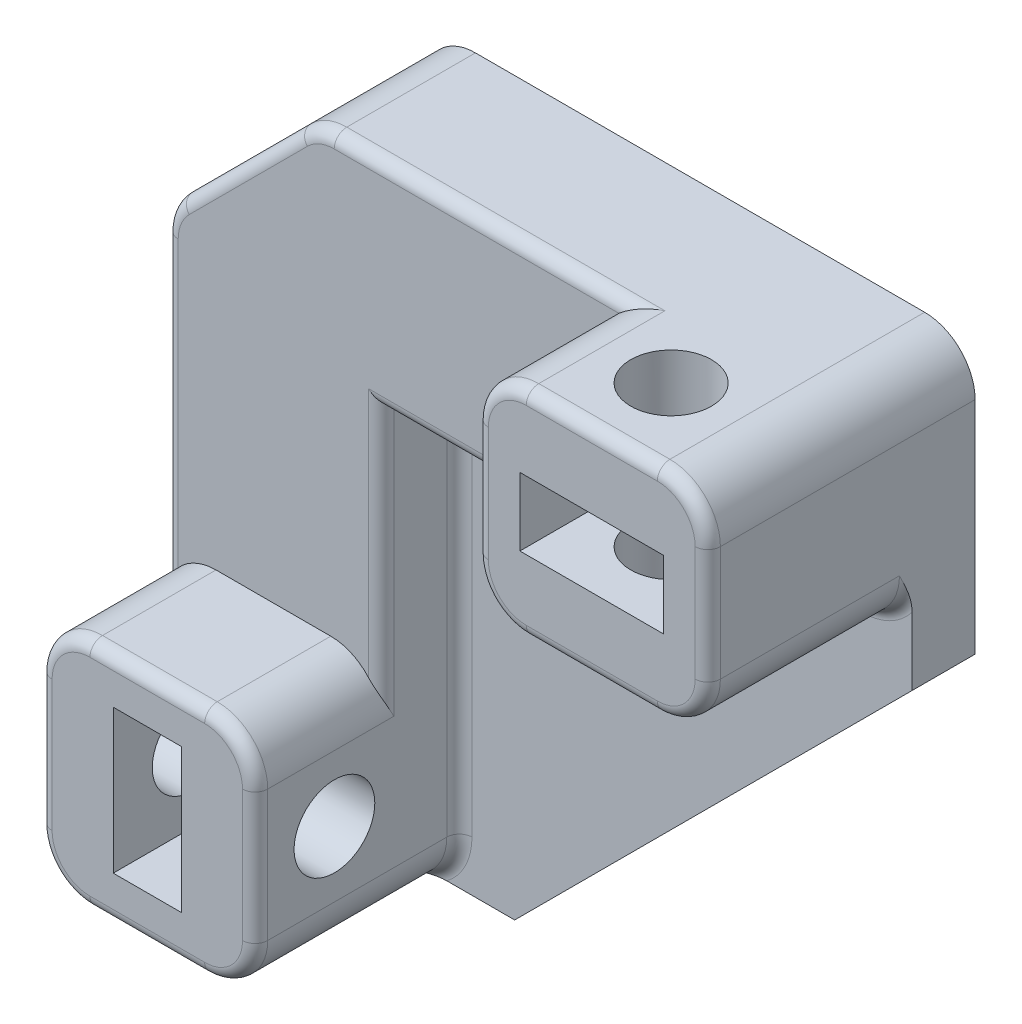
SolidWorks part; units mm, degrees
ref_plane "Plano frontal" through (0, 0, 0) normal (0, 0, 1) x (1, 0, 0)
ref_plane "Plano superior" through (0, 0, 0) normal (0, 1, 0) x (1, 0, 0)
ref_plane "Plano direito" through (0, 0, 0) normal (1, 0, 0) x (0, 0, -1)
sketch "Esboço1" plane through (0, 0, 0) normal (0, 0, 1) x (1, 0, 0)
  line L107 (-13.25, 6.5637) -> (-13.25, -11.25)
  line L117 (-11.25, -13.25) -> (-2.5074, -13.25)
  line L118 (-2.5074, -13.25) -> (13.25, 2.5074)
  line L119 (13.25, 2.5074) -> (13.25, 11.25)
  line L129 (11.25, 13.25) -> (-6.5637, 13.25)
  line L135 (-7.9779, 12.6642) -> (-12.6642, 7.9779)
  circle A0 centre (0, 0) radius 1.7
  arc A1 (13.25, 11.25) -> (11.25, 13.25) centre (11.25, 11.25) ccw
  arc A2 (-6.5637, 13.25) -> (-7.9779, 12.6642) centre (-6.5637, 11.25) ccw
  arc A3 (-12.6642, 7.9779) -> (-13.25, 6.5637) centre (-11.25, 6.5637) ccw
  arc A4 (-13.25, -11.25) -> (-11.25, -13.25) centre (-11.25, -11.25) ccw
  point P23 (-13.25, -13.25)
  dimension "D1" = 3.4
  dimension "D7" = 2
  dimension "D2" = 7.5962
  dimension "D3" = 135
  dimension "D4" = 22.1924
  dimension "D5" = 26.5
  dimension "D6" = 26.5
  dimension "D8" = 10.7426
  dimension "D9" = 13.25
extrude "Ressalto-extrusão1" add sketch "Esboço1" along normal blind 2.5 contours L135 L107 A1 A2 L117 L118 L119 A3 A4 L129 A0 region at (-1.4497, 1.4497, 0)
ref_plane "Plano1" through (0, 0, 2.5) normal (0, 0, -1) x (-1, 0, 0)
sketch "Esboço5" plane through (0, 0, 2.5) normal (0, 0, -1) x (-1, 0, 0)
  line L0 (-11.25, 4.7) -> (4.7, 4.7)
  line L1 (11.25, -13.25) -> (2.5074, -13.25) construction
  line L2 (4.7, 4.7) -> (4.7, -11.25)
  line L3 (-13.25, 2.5074) -> (-13.25, 11.25) construction
  line L4 (-11.25, 13.25) -> (6.5637, 13.25) construction
  line L5 (13.25, 6.5637) -> (13.25, -11.25) construction
  line L6 (7.9779, 12.6642) -> (12.6642, 7.9779) construction
  line L7 (-13.25, 6.7) -> (-13.25, 11.25)
  line L8 (-11.25, 13.25) -> (6.5637, 13.25)
  line L9 (7.9779, 12.6642) -> (12.6642, 7.9779)
  line L10 (13.25, 6.5637) -> (13.25, -11.25)
  line L11 (11.25, -13.25) -> (6.7, -13.25)
  arc A0 (7.9779, 12.6642) -> (6.5637, 13.25) centre (6.5637, 11.25) ccw construction
  arc A1 (11.25, -13.25) -> (13.25, -11.25) centre (11.25, -11.25) ccw
  arc A2 (13.25, 6.5637) -> (12.6642, 7.9779) centre (11.25, 6.5637) ccw
  arc A3 (7.9779, 12.6642) -> (6.5637, 13.25) centre (6.5637, 11.25) ccw
  arc A8 (4.7, -11.25) -> (6.7, -13.25) centre (6.7, -11.25) ccw
  arc A9 (-11.25, 4.7) -> (-13.25, 6.7) centre (-11.25, 6.7) cw
  arc A10 (-11.25, 13.25) -> (-13.25, 11.25) centre (-11.25, 11.25) ccw
  point P19 (4.7, -13.25)
  point P22 (-13.25, 4.7)
  dimension "D3" = 2
  dimension "D1" = 8.55
  dimension "D2" = 8.55
extrude "Ressalto-extrusão3" add sketch "Esboço5" against normal blind 3.1
sketch "Esboço6" plane through (0, 0, 5.6) normal (0, 0, 1) x (1, 0, 0)
  line L0 (-6.7, -4.05) -> (-11.25, -4.05)
  line L1 (-4.7, 4.7) -> (-4.7, -11.25) construction
  line L2 (-13.25, -11.25) -> (-13.25, 6.5637) construction
  line L3 (-6.7, -13.25) -> (-11.25, -13.25) construction
  line L4 (4.05, 6.7) -> (4.05, 11.25)
  line L5 (11.25, 4.7) -> (-4.7, 4.7) construction
  line L6 (-6.5637, 13.25) -> (11.25, 13.25) construction
  line L7 (13.25, 11.25) -> (13.25, 6.7) construction
  line L15 (-4.7, -11.25) -> (-4.7, 4.7)
  line L16 (-4.7, 4.7) -> (11.25, 4.7)
  line L17 (13.25, 6.7) -> (13.25, 11.25)
  line L18 (11.25, 13.25) -> (-6.5637, 13.25)
  line L19 (-7.9779, 12.6642) -> (-12.6642, 7.9779)
  line L20 (-13.25, 6.5637) -> (-13.25, -11.25)
  line L21 (-11.25, -13.25) -> (-6.7, -13.25)
  line L22 (-4.7, -11.25) -> (-4.7, -6.05)
  line L23 (6.05, 4.7) -> (11.25, 4.7)
  line L24 (13.25, 6.7) -> (13.25, 11.25)
  line L25 (11.25, 13.25) -> (6.05, 13.25)
  line L27 (-13.25, -6.05) -> (-13.25, -11.25)
  line L28 (-11.25, -13.25) -> (-6.7, -13.25)
  arc A0 (4.05, 11.25) -> (6.05, 13.25) centre (6.05, 11.25) cw
  arc A1 (4.05, 6.7) -> (6.05, 4.7) centre (6.05, 6.7) ccw
  arc A2 (-6.7, -4.05) -> (-4.7, -6.05) centre (-6.7, -6.05) cw
  arc A3 (-11.25, -4.05) -> (-13.25, -6.05) centre (-11.25, -6.05) ccw
  arc A6 (11.25, 4.7) -> (13.25, 6.7) centre (11.25, 6.7) ccw
  arc A7 (13.25, 11.25) -> (11.25, 13.25) centre (11.25, 11.25) ccw
  arc A8 (-6.5637, 13.25) -> (-7.9779, 12.6642) centre (-6.5637, 11.25) ccw
  arc A9 (-12.6642, 7.9779) -> (-13.25, 6.5637) centre (-11.25, 6.5637) ccw
  arc A10 (-13.25, -11.25) -> (-11.25, -13.25) centre (-11.25, -11.25) ccw
  arc A11 (-6.7, -13.25) -> (-4.7, -11.25) centre (-6.7, -11.25) ccw
  arc A12 (11.25, 4.7) -> (13.25, 6.7) centre (11.25, 6.7) ccw
  arc A13 (13.25, 11.25) -> (11.25, 13.25) centre (11.25, 11.25) ccw
  arc A16 (-13.25, -11.25) -> (-11.25, -13.25) centre (-11.25, -11.25) ccw
  arc A17 (-6.7, -13.25) -> (-4.7, -11.25) centre (-6.7, -11.25) ccw
  point P23 (4.05, 13.25)
  point P32 (4.05, 4.7)
  point P43 (-4.7, -4.05)
  point P46 (-13.25, -4.05)
  dimension "D4" = 2
  dimension "D1" = 9.2
  dimension "D2" = 9.2
  dimension "D3" = 0
extrude "Ressalto-extrusão4" add sketch "Esboço6" along normal blind 5
sketch "Esboço7" plane through (-4.7, 0, 0) normal (1, 0, 0) x (0, 0, -1)
  line L0 (-2.5, -8.65) -> (-5.854, -8.65) construction
  line L3 (-2.5, 4.7) -> (-2.5, -11.25) construction
  circle A0 centre (-7.454, -8.65) radius 1.6
  dimension "D1" = 3.2
  dimension "D2" = 3.354
extrude "Corte-extrusão3" cut sketch "Esboço7" against normal through all
ref_plane "Plano2" through (0, 0, 0) normal (-0.7071, -0.7071, 0) x (-0.7071, 0.7071, 0)
mirror "Espelhar1" about plane through (0, 0, 0) normal (-0.7071, -0.7071, 0) of "Corte-extrusão3"
fillet "Filete3" radius 0.5 27 edges at (12.6642, 5.2858, 2.5) (-5.2858, -12.6642, 2.5) (12.6642, 5.2858, 10.6) (8.65, 4.7, 10.6) (4.6358, 5.2858, 10.6) (4.05, 8.975, 10.6) (4.6358, 12.6642, 10.6) (8.65, 13.25, 10.6) (12.6642, 12.6642, 10.6) (-0.2569, 13.25, 5.6) (-7.3291, 13.0978, 5.6) (-10.3211, 10.3211, 5.6) (-13.0978, 7.3291, 5.6) (-5.2858, -12.6642, 10.6) (-8.975, -13.25, 10.6) (-12.6642, -12.6642, 10.6) (-13.25, -8.65, 10.6) (-12.6642, -4.6358, 10.6) (-8.975, -4.05, 10.6) (-5.2858, -4.6358, 10.6) (3.275, 4.7, 2.5) (-4.7, -3.275, 2.5) (-4.7, -0.675, 5.6) (0.675, 4.7, 5.6) (13.25, 8.975, 10.6) (-13.25, 0.2569, 5.6) (-4.7, -8.65, 10.6)
ref_plane "Plano3" through (-8.975, 0, 0) normal (1, 0, 0) x (0, 0, -1)
sketch "Esboço10" plane through (-8.975, 0, 0) normal (1, 0, 0) x (0, 0, -1)
  line L0 (-9.0994, -5.8) -> (-13.6026, -5.8)
  line L1 (-4.1631, -8.65) -> (-5.8086, -5.8)
  line L2 (-5.8086, -5.8) -> (-9.0994, -5.8)
  line L3 (-9.0994, -5.8) -> (-10.7449, -8.65) construction
  line L4 (-10.7449, -8.65) -> (-9.0994, -11.5) construction
  line L5 (-9.0994, -11.5) -> (-5.8086, -11.5)
  line L6 (-5.8086, -11.5) -> (-4.1631, -8.65)
  line L7 (-13.6026, -5.8) -> (-13.6026, -11.5)
  line L8 (-13.6026, -11.5) -> (-9.0994, -11.5)
  circle A0 centre (-7.454, -8.65) radius 2.85 construction
  dimension "D1" = 5.7
  dimension "D2" = 4.5031
extrude "Corte-extrusão4" cut sketch "Esboço10" against normal mid plane 2.7
mirror "Espelhar2" about plane through (0, 0, 0) normal (-0.7071, -0.7071, 0) of "Corte-extrusão4"
